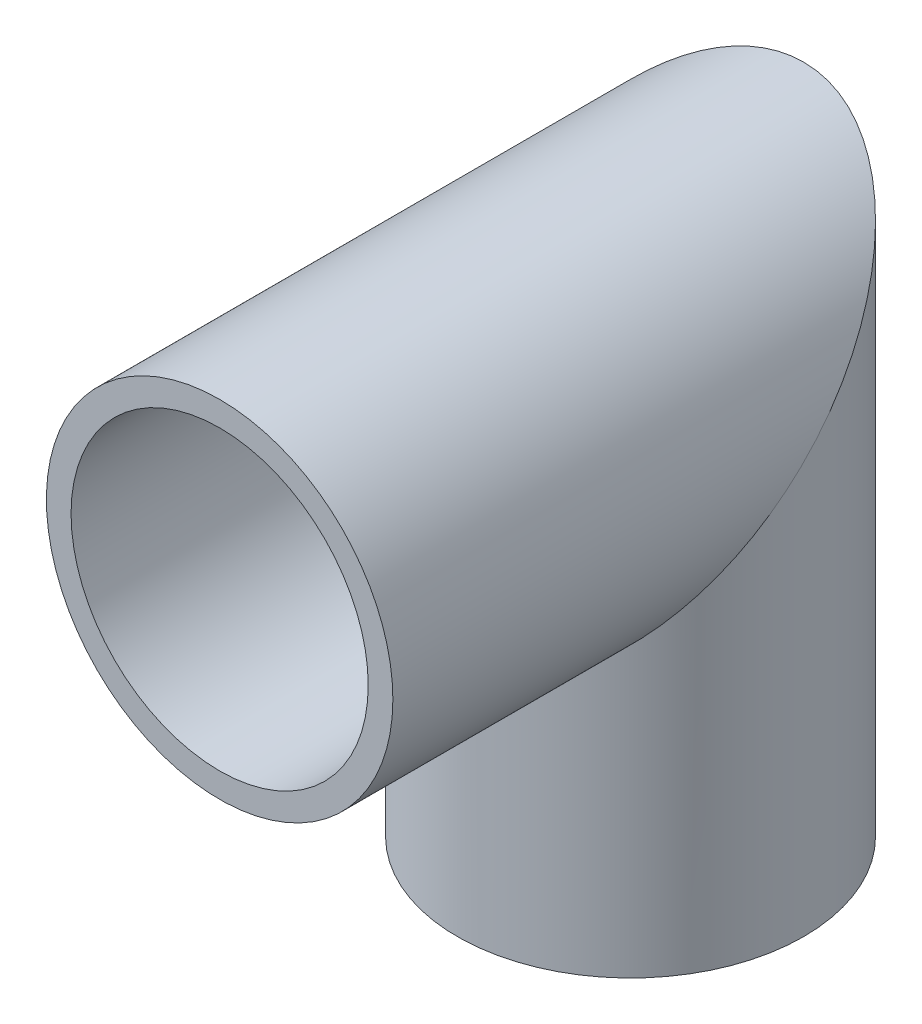
SolidWorks part; units mm, degrees
ref_plane "Front Plane" through (0, 0, 0) normal (0, 0, 1) x (1, 0, 0)
ref_plane "Top Plane" through (0, 0, 0) normal (0, 1, 0) x (1, 0, 0)
ref_plane "Right Plane" through (0, 0, 0) normal (1, 0, 0) x (0, 0, -1)
sketch "Sketch1" plane through (0, 0, 0) normal (0, 0, 1) x (1, 0, 0)
  circle A0 centre (0, 0) radius 21.08
  dimension "D1" = 42.16
sketch "Sketch2" plane through (0, 0, 0) normal (1, 0, 0) x (0, 0, -1)
  line L0 (0, 0) -> (50, 0)
  line L1 (20.0904, 0) -> (-20.0904, 0) construction
  line L2 (50, 0) -> (50, -50)
  dimension "D1" = 50
  dimension "D2" = 50
sweep "Sweep1" add profiles "Sketch1" path "Sketch2"
shell "Shell1" thickness 3 removed face at (21.08, 0, 0)
sketch "Sketch3" plane through (0, -50, 0) normal (0, -1, 0) x (1, 0, 0)
  line L0 (6.5989, -37.2613) -> (6.5989, -38.8787)
  line L1 (9.5989, -37.2613) -> (8.4034, -37.2613)
  line L2 (9.5989, -37.2613) -> (9.5989, -38.8787)
  line L3 (9.5989, -38.8787) -> (8.4034, -38.8787)
  line L4 (8.4034, -37.2613) -> (8.4034, -38.8787)
  line L5 (6.5989, -37.2613) -> (5.4034, -37.2613)
  line L6 (5.4034, -37.2613) -> (5.4034, -38.8787)
  line L7 (6.5989, -38.8787) -> (5.4034, -38.8787)
  line L8 (3.5989, -37.2613) -> (3.5989, -38.8787)
  line L9 (3.5989, -37.2613) -> (2.4034, -37.2613)
  line L10 (2.4034, -37.2613) -> (2.4034, -38.8787)
  line L11 (3.5989, -38.8787) -> (2.4034, -38.8787)
  line L12 (0.5989, -37.2613) -> (0.5989, -38.8787)
  line L13 (0.5989, -37.2613) -> (-0.5966, -37.2613)
  line L14 (-0.5966, -37.2613) -> (-0.5966, -38.8787)
  line L15 (0.5989, -38.8787) -> (-0.5966, -38.8787)
  line L16 (-2.4011, -37.2613) -> (-2.4011, -38.8787)
  line L17 (-2.4011, -37.2613) -> (-3.5966, -37.2613)
  line L18 (-3.5966, -37.2613) -> (-3.5966, -38.8787)
  line L19 (-2.4011, -38.8787) -> (-3.5966, -38.8787)
  line L20 (-5.4011, -37.2613) -> (-5.4011, -38.8787)
  line L21 (-5.4011, -37.2613) -> (-6.5966, -37.2613)
  line L22 (-6.5966, -37.2613) -> (-6.5966, -38.8787)
  line L23 (-5.4011, -38.8787) -> (-6.5966, -38.8787)
  line L24 (-8.4011, -37.2613) -> (-8.4011, -38.8787)
  line L25 (-8.4011, -37.2613) -> (-9.5966, -37.2613)
  line L26 (-9.5966, -37.2613) -> (-9.5966, -38.8787)
  line L27 (-8.4011, -38.8787) -> (-9.5966, -38.8787)
  line L28 (6.5989, -40.2613) -> (6.5989, -41.8787)
  line L29 (6.5989, -40.2613) -> (5.4034, -40.2613)
  line L30 (5.4034, -40.2613) -> (5.4034, -41.8787)
  line L31 (6.5989, -41.8787) -> (5.4034, -41.8787)
  line L32 (3.5989, -40.2613) -> (3.5989, -41.8787)
  line L33 (3.5989, -40.2613) -> (2.4034, -40.2613)
  line L34 (2.4034, -40.2613) -> (2.4034, -41.8787)
  line L35 (3.5989, -41.8787) -> (2.4034, -41.8787)
  line L36 (0.5989, -40.2613) -> (0.5989, -41.8787)
  line L37 (0.5989, -40.2613) -> (-0.5966, -40.2613)
  line L38 (-0.5966, -40.2613) -> (-0.5966, -41.8787)
  line L39 (0.5989, -41.8787) -> (-0.5966, -41.8787)
  line L40 (-2.4011, -40.2613) -> (-2.4011, -41.8787)
  line L41 (-2.4011, -40.2613) -> (-3.5966, -40.2613)
  line L42 (-3.5966, -40.2613) -> (-3.5966, -41.8787)
  line L43 (-2.4011, -41.8787) -> (-3.5966, -41.8787)
  line L44 (-5.4011, -40.2613) -> (-5.4011, -41.8787)
  line L45 (-5.4011, -40.2613) -> (-6.5966, -40.2613)
  line L46 (-6.5966, -40.2613) -> (-6.5966, -41.8787)
  line L47 (-5.4011, -41.8787) -> (-6.5966, -41.8787)
  line L48 (-8.4011, -40.2613) -> (-8.4011, -41.8787)
  line L49 (-8.4011, -40.2613) -> (-9.5966, -40.2613)
  line L50 (-9.5966, -40.2613) -> (-9.5966, -41.8787)
  line L51 (-8.4011, -41.8787) -> (-9.5966, -41.8787)
  line L52 (6.5989, -43.2613) -> (6.5989, -44.8787)
  line L53 (6.5989, -43.2613) -> (5.4034, -43.2613)
  line L54 (5.4034, -43.2613) -> (5.4034, -44.8787)
  line L55 (6.5989, -44.8787) -> (5.4034, -44.8787)
  line L56 (3.5989, -43.2613) -> (3.5989, -44.8787)
  line L57 (3.5989, -43.2613) -> (2.4034, -43.2613)
  line L58 (2.4034, -43.2613) -> (2.4034, -44.8787)
  line L59 (3.5989, -44.8787) -> (2.4034, -44.8787)
  line L60 (0.5989, -43.2613) -> (0.5989, -44.8787)
  line L61 (0.5989, -43.2613) -> (-0.5966, -43.2613)
  line L62 (-0.5966, -43.2613) -> (-0.5966, -44.8787)
  line L63 (0.5989, -44.8787) -> (-0.5966, -44.8787)
  line L64 (-2.4011, -43.2613) -> (-2.4011, -44.8787)
  line L65 (-2.4011, -43.2613) -> (-3.5966, -43.2613)
  line L66 (-3.5966, -43.2613) -> (-3.5966, -44.8787)
  line L67 (-2.4011, -44.8787) -> (-3.5966, -44.8787)
  line L68 (-5.4011, -43.2613) -> (-5.4011, -44.8787)
  line L69 (-5.4011, -43.2613) -> (-6.5966, -43.2613)
  line L70 (-6.5966, -43.2613) -> (-6.5966, -44.8787)
  line L71 (-5.4011, -44.8787) -> (-6.5966, -44.8787)
  line L72 (-8.4011, -43.2613) -> (-8.4011, -44.8787)
  line L73 (-8.4011, -43.2613) -> (-9.5966, -43.2613)
  line L74 (-9.5966, -43.2613) -> (-9.5966, -44.8787)
  line L75 (-8.4011, -44.8787) -> (-9.5966, -44.8787)
  line L76 (6.5989, -46.2613) -> (6.5989, -47.8787)
  line L77 (6.5989, -46.2613) -> (5.4034, -46.2613)
  line L78 (5.4034, -46.2613) -> (5.4034, -47.8787)
  line L79 (6.5989, -47.8787) -> (5.4034, -47.8787)
  line L80 (3.5989, -46.2613) -> (3.5989, -47.8787)
  line L81 (3.5989, -46.2613) -> (2.4034, -46.2613)
  line L82 (2.4034, -46.2613) -> (2.4034, -47.8787)
  line L83 (3.5989, -47.8787) -> (2.4034, -47.8787)
  line L84 (0.5989, -46.2613) -> (0.5989, -47.8787)
  line L85 (0.5989, -46.2613) -> (-0.5966, -46.2613)
  line L86 (-0.5966, -46.2613) -> (-0.5966, -47.8787)
  line L87 (0.5989, -47.8787) -> (-0.5966, -47.8787)
  line L88 (-2.4011, -46.2613) -> (-2.4011, -47.8787)
  line L89 (-2.4011, -46.2613) -> (-3.5966, -46.2613)
  line L90 (-3.5966, -46.2613) -> (-3.5966, -47.8787)
  line L91 (-2.4011, -47.8787) -> (-3.5966, -47.8787)
  line L92 (-5.4011, -46.2613) -> (-5.4011, -47.8787)
  line L93 (-5.4011, -46.2613) -> (-6.5966, -46.2613)
  line L94 (-6.5966, -46.2613) -> (-6.5966, -47.8787)
  line L95 (-5.4011, -47.8787) -> (-6.5966, -47.8787)
  line L96 (-8.4011, -46.2613) -> (-8.4011, -47.8787)
  line L97 (-8.4011, -46.2613) -> (-9.5966, -46.2613)
  line L98 (-9.5966, -46.2613) -> (-9.5966, -47.8787)
  line L99 (-8.4011, -47.8787) -> (-9.5966, -47.8787)
  line L100 (6.5989, -49.2613) -> (6.5989, -50.8787)
  line L101 (6.5989, -49.2613) -> (5.4034, -49.2613)
  line L102 (5.4034, -49.2613) -> (5.4034, -50.8787)
  line L103 (6.5989, -50.8787) -> (5.4034, -50.8787)
  line L104 (3.5989, -49.2613) -> (3.5989, -50.8787)
  line L105 (3.5989, -49.2613) -> (2.4034, -49.2613)
  line L106 (2.4034, -49.2613) -> (2.4034, -50.8787)
  line L107 (3.5989, -50.8787) -> (2.4034, -50.8787)
  line L108 (0.5989, -49.2613) -> (0.5989, -50.8787)
  line L109 (0.5989, -49.2613) -> (-0.5966, -49.2613)
  line L110 (-0.5966, -49.2613) -> (-0.5966, -50.8787)
  line L111 (0.5989, -50.8787) -> (-0.5966, -50.8787)
  line L112 (-2.4011, -49.2613) -> (-2.4011, -50.8787)
  line L113 (-2.4011, -49.2613) -> (-3.5966, -49.2613)
  line L114 (-3.5966, -49.2613) -> (-3.5966, -50.8787)
  line L115 (-2.4011, -50.8787) -> (-3.5966, -50.8787)
  line L116 (-5.4011, -49.2613) -> (-5.4011, -50.8787)
  line L117 (-5.4011, -49.2613) -> (-6.5966, -49.2613)
  line L118 (-6.5966, -49.2613) -> (-6.5966, -50.8787)
  line L119 (-5.4011, -50.8787) -> (-6.5966, -50.8787)
  line L120 (-8.4011, -49.2613) -> (-8.4011, -50.8787)
  line L121 (-8.4011, -49.2613) -> (-9.5966, -49.2613)
  line L122 (-9.5966, -49.2613) -> (-9.5966, -50.8787)
  line L123 (-8.4011, -50.8787) -> (-9.5966, -50.8787)
  line L124 (6.5989, -52.2613) -> (6.5989, -53.8787)
  line L125 (6.5989, -52.2613) -> (5.4034, -52.2613)
  line L126 (5.4034, -52.2613) -> (5.4034, -53.8787)
  line L127 (6.5989, -53.8787) -> (5.4034, -53.8787)
  line L128 (3.5989, -52.2613) -> (3.5989, -53.8787)
  line L129 (3.5989, -52.2613) -> (2.4034, -52.2613)
  line L130 (2.4034, -52.2613) -> (2.4034, -53.8787)
  line L131 (3.5989, -53.8787) -> (2.4034, -53.8787)
  line L132 (0.5989, -52.2613) -> (0.5989, -53.8787)
  line L133 (0.5989, -52.2613) -> (-0.5966, -52.2613)
  line L134 (-0.5966, -52.2613) -> (-0.5966, -53.8787)
  line L135 (0.5989, -53.8787) -> (-0.5966, -53.8787)
  line L136 (-2.4011, -52.2613) -> (-2.4011, -53.8787)
  line L137 (-2.4011, -52.2613) -> (-3.5966, -52.2613)
  line L138 (-3.5966, -52.2613) -> (-3.5966, -53.8787)
  line L139 (-2.4011, -53.8787) -> (-3.5966, -53.8787)
  line L140 (-5.4011, -52.2613) -> (-5.4011, -53.8787)
  line L141 (-5.4011, -52.2613) -> (-6.5966, -52.2613)
  line L142 (-6.5966, -52.2613) -> (-6.5966, -53.8787)
  line L143 (-5.4011, -53.8787) -> (-6.5966, -53.8787)
  line L144 (-8.4011, -52.2613) -> (-8.4011, -53.8787)
  line L145 (-8.4011, -52.2613) -> (-9.5966, -52.2613)
  line L146 (-9.5966, -52.2613) -> (-9.5966, -53.8787)
  line L147 (-8.4011, -53.8787) -> (-9.5966, -53.8787)
  line L148 (6.5989, -55.2613) -> (6.5989, -56.8787)
  line L149 (6.5989, -55.2613) -> (5.4034, -55.2613)
  line L150 (5.4034, -55.2613) -> (5.4034, -56.8787)
  line L151 (6.5989, -56.8787) -> (5.4034, -56.8787)
  line L152 (3.5989, -55.2613) -> (3.5989, -56.8787)
  line L153 (3.5989, -55.2613) -> (2.4034, -55.2613)
  line L154 (2.4034, -55.2613) -> (2.4034, -56.8787)
  line L155 (3.5989, -56.8787) -> (2.4034, -56.8787)
  line L156 (0.5989, -55.2613) -> (0.5989, -56.8787)
  line L157 (0.5989, -55.2613) -> (-0.5966, -55.2613)
  line L158 (-0.5966, -55.2613) -> (-0.5966, -56.8787)
  line L159 (0.5989, -56.8787) -> (-0.5966, -56.8787)
  line L160 (-2.4011, -55.2613) -> (-2.4011, -56.8787)
  line L161 (-2.4011, -55.2613) -> (-3.5966, -55.2613)
  line L162 (-3.5966, -55.2613) -> (-3.5966, -56.8787)
  line L163 (-2.4011, -56.8787) -> (-3.5966, -56.8787)
  line L164 (-5.4011, -55.2613) -> (-5.4011, -56.8787)
  line L165 (-5.4011, -55.2613) -> (-6.5966, -55.2613)
  line L166 (-6.5966, -55.2613) -> (-6.5966, -56.8787)
  line L167 (-5.4011, -56.8787) -> (-6.5966, -56.8787)
  line L168 (-8.4011, -55.2613) -> (-8.4011, -56.8787)
  line L169 (-8.4011, -55.2613) -> (-9.5966, -55.2613)
  line L170 (-9.5966, -55.2613) -> (-9.5966, -56.8787)
  line L171 (-8.4011, -56.8787) -> (-9.5966, -56.8787)
  line L172 (6.5989, -58.2613) -> (6.5989, -59.8787)
  line L173 (6.5989, -58.2613) -> (5.4034, -58.2613)
  line L174 (5.4034, -58.2613) -> (5.4034, -59.8787)
  line L175 (6.5989, -59.8787) -> (5.4034, -59.8787)
  line L176 (3.5989, -58.2613) -> (3.5989, -59.8787)
  line L177 (3.5989, -58.2613) -> (2.4034, -58.2613)
  line L178 (2.4034, -58.2613) -> (2.4034, -59.8787)
  line L179 (3.5989, -59.8787) -> (2.4034, -59.8787)
  line L180 (0.5989, -58.2613) -> (0.5989, -59.8787)
  line L181 (0.5989, -58.2613) -> (-0.5966, -58.2613)
  line L182 (-0.5966, -58.2613) -> (-0.5966, -59.8787)
  line L183 (0.5989, -59.8787) -> (-0.5966, -59.8787)
  line L184 (-2.4011, -58.2613) -> (-2.4011, -59.8787)
  line L185 (-2.4011, -58.2613) -> (-3.5966, -58.2613)
  line L186 (-3.5966, -58.2613) -> (-3.5966, -59.8787)
  line L187 (-2.4011, -59.8787) -> (-3.5966, -59.8787)
  line L188 (-5.4011, -58.2613) -> (-5.4011, -59.8787)
  line L189 (-5.4011, -58.2613) -> (-6.5966, -58.2613)
  line L190 (-6.5966, -58.2613) -> (-6.5966, -59.8787)
  line L191 (-5.4011, -59.8787) -> (-6.5966, -59.8787)
  line L192 (-8.4011, -58.2613) -> (-8.4011, -59.8787)
  line L193 (-8.4011, -58.2613) -> (-9.5966, -58.2613)
  line L194 (-9.5966, -58.2613) -> (-9.5966, -59.8787)
  line L195 (-8.4011, -59.8787) -> (-9.5966, -59.8787)
  line L196 (6.5989, -61.2613) -> (6.5989, -62.8786)
  line L197 (6.5989, -61.2613) -> (5.4034, -61.2613)
  line L198 (5.4034, -61.2613) -> (5.4034, -62.8786)
  line L199 (6.5989, -62.8786) -> (5.4034, -62.8786)
  line L200 (3.5989, -61.2613) -> (3.5989, -62.8786)
  line L201 (3.5989, -61.2613) -> (2.4034, -61.2613)
  line L202 (2.4034, -61.2613) -> (2.4034, -62.8786)
  line L203 (3.5989, -62.8786) -> (2.4034, -62.8786)
  line L204 (0.5989, -61.2613) -> (0.5989, -62.8786)
  line L205 (0.5989, -61.2613) -> (-0.5966, -61.2613)
  line L206 (-0.5966, -61.2613) -> (-0.5966, -62.8786)
  line L207 (0.5989, -62.8786) -> (-0.5966, -62.8786)
  line L208 (-2.4011, -61.2613) -> (-2.4011, -62.8786)
  line L209 (-2.4011, -61.2613) -> (-3.5966, -61.2613)
  line L210 (-3.5966, -61.2613) -> (-3.5966, -62.8786)
  line L211 (-2.4011, -62.8786) -> (-3.5966, -62.8786)
  line L212 (-5.4011, -61.2613) -> (-5.4011, -62.8786)
  line L213 (-5.4011, -61.2613) -> (-6.5966, -61.2613)
  line L214 (-6.5966, -61.2613) -> (-6.5966, -62.8786)
  line L215 (-5.4011, -62.8786) -> (-6.5966, -62.8786)
  line L216 (-8.4011, -61.2613) -> (-8.4011, -62.8786)
  line L217 (-8.4011, -61.2613) -> (-9.5966, -61.2613)
  line L218 (-9.5966, -61.2613) -> (-9.5966, -62.8786)
  line L219 (-8.4011, -62.8786) -> (-9.5966, -62.8786)
  line L220 (9.5989, -40.2613) -> (9.5989, -41.8787)
  line L221 (9.5989, -40.2613) -> (8.4034, -40.2613)
  line L222 (8.4034, -40.2613) -> (8.4034, -41.8787)
  line L223 (9.5989, -41.8787) -> (8.4034, -41.8787)
  line L224 (9.5989, -43.2613) -> (9.5989, -44.8787)
  line L225 (9.5989, -43.2613) -> (8.4034, -43.2613)
  line L226 (8.4034, -43.2613) -> (8.4034, -44.8787)
  line L227 (9.5989, -44.8787) -> (8.4034, -44.8787)
  line L228 (9.5989, -46.2613) -> (9.5989, -47.8787)
  line L229 (9.5989, -46.2613) -> (8.4034, -46.2613)
  line L230 (8.4034, -46.2613) -> (8.4034, -47.8787)
  line L231 (9.5989, -47.8787) -> (8.4034, -47.8787)
  line L232 (9.5989, -49.2613) -> (9.5989, -50.8787)
  line L233 (9.5989, -49.2613) -> (8.4034, -49.2613)
  line L234 (8.4034, -49.2613) -> (8.4034, -50.8787)
  line L235 (9.5989, -50.8787) -> (8.4034, -50.8787)
  line L236 (9.5989, -52.2613) -> (9.5989, -53.8787)
  line L237 (9.5989, -52.2613) -> (8.4034, -52.2613)
  line L238 (8.4034, -52.2613) -> (8.4034, -53.8787)
  line L239 (9.5989, -53.8787) -> (8.4034, -53.8787)
  line L240 (9.5989, -55.2613) -> (9.5989, -56.8787)
  line L241 (9.5989, -55.2613) -> (8.4034, -55.2613)
  line L242 (8.4034, -55.2613) -> (8.4034, -56.8787)
  line L243 (9.5989, -56.8787) -> (8.4034, -56.8787)
  line L244 (9.5989, -58.2613) -> (9.5989, -59.8787)
  line L245 (9.5989, -58.2613) -> (8.4034, -58.2613)
  line L246 (8.4034, -58.2613) -> (8.4034, -59.8787)
  line L247 (9.5989, -59.8787) -> (8.4034, -59.8787)
  line L248 (9.5989, -61.2613) -> (9.5989, -62.8786)
  line L249 (9.5989, -61.2613) -> (8.4034, -61.2613)
  line L250 (8.4034, -61.2613) -> (8.4034, -62.8786)
  line L251 (9.5989, -62.8786) -> (8.4034, -62.8786)
  dimension "D1" = 7
  dimension "D2" = 9
extrude "Cut-Extrude1" cut sketch "Sketch3" against normal blind 20
